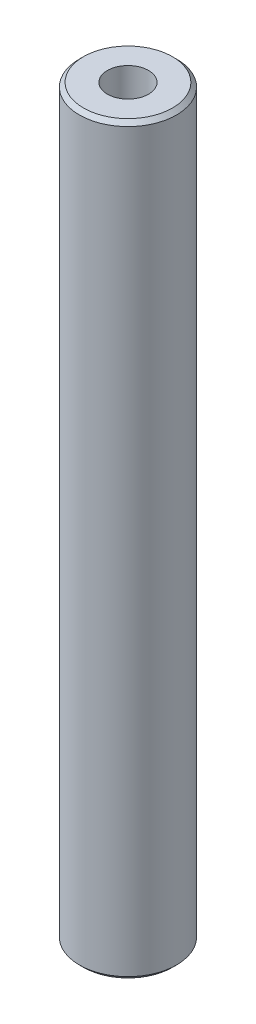
SolidWorks part; units mm, degrees
material "6061-T6 (SS)"
ref_plane "Alzado" through (0, 0, 0) normal (0, 0, 1) x (1, 0, 0)
ref_plane "Planta" through (0, 0, 0) normal (0, 1, 0) x (1, 0, 0)
ref_plane "Vista lateral" through (0, 0, 0) normal (1, 0, 0) x (0, 0, -1)
sketch "Croquis2" plane through (0, 0, 0) normal (0, 1, 0) x (1, 0, 0)
  circle A0 centre (0, 0) radius 4.7625
  dimension "D1" = 9.525
extrude "Saliente-Extruir1" add sketch "Croquis2" along normal mid plane 73.025
chamfer "Chaflán1" distance 0.3969 angle 45 2 edges at (0, -36.5125, 4.7625) (0, 36.5125, 4.7625)
sketch "Croquis3" plane through (0, 0, 0) normal (0, 1, 0) x (1, 0, 0)
  circle A0 centre (0, 0) radius 2.0193
  dimension "D1" = 4.0386
extrude "Tap Hole 1" cut sketch "Croquis3" against normal blind 19.05 from surface starting at face at (0, 36.5125, 4.3656)
extrude "Tap Hole 2" cut sketch "Croquis3<2>" along normal blind 19.05 from surface starting at face at (0, -36.5125, 4.3656)
sketch "Croquis3<2>" plane through (0, 0, 0) normal (0, 1, 0) x (1, 0, 0) same geometry as "Croquis3"
sketch "Croquis4" plane through (0, 0, 0) normal (0, 1, 0) x (1, 0, 0)
  circle A0 centre (0, 0) radius 2.4892
  dimension "D1" = 4.9784
extrude "Clearance Hole" [suppressed] cut sketch "Croquis4" against normal through all both and the other way through all
equation "\"OD\"= 0.375pulgadas"
equation "\"Largo\"= 2.875pulgadas"
equation "\"Tap Hole\"= IIF ( \"OD\" = 0.375pulgadas , 0.1590pulgadas , 0.201pulgadas )"
equation "\"Spacer Hole\"= IIF ( \"OD\" = 0.375pulgadas , 0.196pulgadas , 0.257pulgadas )"
equation "\"D1@Croquis2\"=\"OD\""
equation "\"D1@Saliente-Extruir1\"=\"Largo\""
equation "\"D1@Croquis3\"=\"Tap Hole\""
equation "\"D1@Croquis4\"=\"Spacer Hole\""
